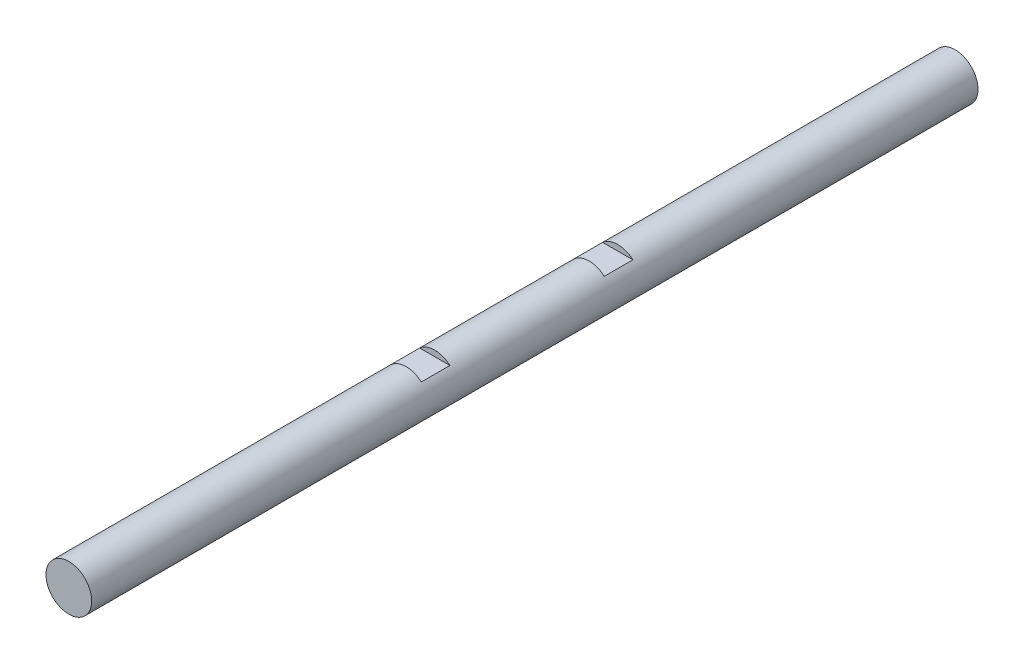
SolidWorks part; units mm, degrees
material "AISI 316 Stainless Steel Sheet (SS)"
ref_plane "Front Plane" through (0, 0, 0) normal (0, 0, 1) x (1, 0, 0)
ref_plane "Top Plane" through (0, 0, 0) normal (0, 1, 0) x (1, 0, 0)
ref_plane "Right Plane" through (0, 0, 0) normal (1, 0, 0) x (0, 0, -1)
sketch "Sketch1" plane through (0, 0, 0) normal (0, 0, 1) x (1, 0, 0)
  circle A0 centre (0, 0) radius 4
  dimension "D1" = 8
extrude "Boss-Extrude1" add sketch "Sketch1" along normal blind 77.5 and the other way blind 77.5
sketch "Sketch3" plane through (0, 0, 0) normal (1, 0, 0) x (0, 0, -1)
  line L0 (77.5, 4) -> (-77.5, 4) construction
  line L1 (18.5, 4) -> (13.5, 4)
  line L2 (18.5, 4) -> (18.5, 3)
  line L3 (18.5, 3) -> (13.5, 3)
  line L4 (13.5, 4) -> (13.5, 3)
  line L5 (77.5, -4) -> (77.5, 4) construction
  line L6 (-13.5, 4) -> (-18.5, 4)
  line L7 (-13.5, 4) -> (-13.5, 3)
  line L8 (-13.5, 3) -> (-18.5, 3)
  line L9 (-18.5, 4) -> (-18.5, 3)
  line L15 (77.5, 4) -> (-77.5, 4) construction
  point P6 (0, 0)
  dimension "D1" = 5
  dimension "D2" = 1
  dimension "D3" = 37
  dimension "D4" = 59
extrude "Cut-Extrude1" cut sketch "Sketch3" against normal through all both and the other way through all
